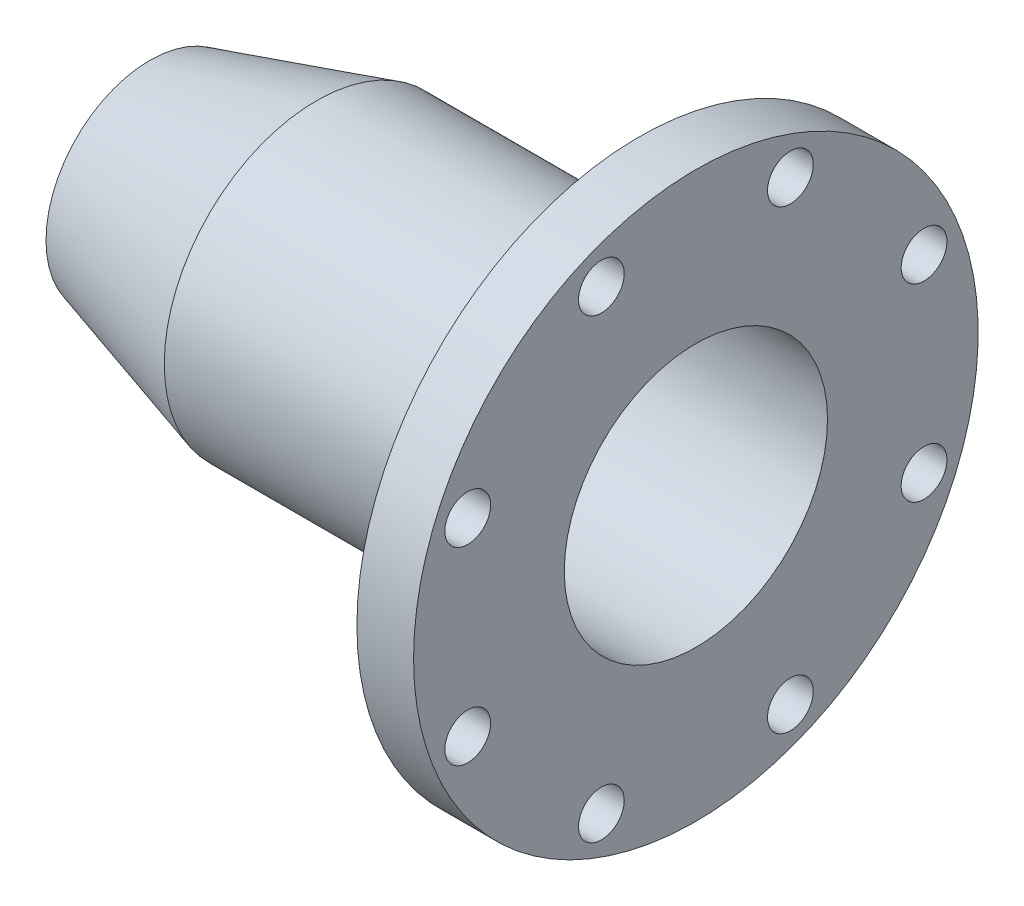
SolidWorks part; units mm, degrees
ref_plane "Front Plane" through (0, 0, 0) normal (0, 0, 1) x (1, 0, 0)
ref_plane "Top Plane" through (0, 0, 0) normal (0, 1, 0) x (1, 0, 0)
ref_plane "Right Plane" through (0, 0, 0) normal (1, 0, 0) x (0, 0, -1)
sketch "Sketch1" plane through (0, 0, 0) normal (0, 0, 1) x (1, 0, 0)
  line L0 (0, 0) -> (541.4119, 0) construction
  line L1 (266.7, 64.295) -> (266.7, 137.92)
  line L2 (266.7, 137.92) -> (239.01, 137.92)
  line L3 (239.01, 137.92) -> (239.01, 74.295)
  line L4 (239.01, 74.295) -> (81.28, 74.295)
  line L5 (239.01, 64.295) -> (82.6963, 64.295)
  line L6 (239.01, 64.295) -> (266.7, 64.295)
  line L7 (81.28, 74.295) -> (0, 50.8)
  line L8 (82.6963, 64.295) -> (0, 40.3906)
  line L9 (0, 50.8) -> (0, 40.3906)
  dimension "D2" = 27.69
  dimension "D3" = 74.295
  dimension "D4" = 185.42
  dimension "D5" = 266.7
  dimension "D6" = 10
  dimension "D1" = 50.8
  dimension "D7" = 10
revolve "Revolve1" add sketch "Sketch1" angle 360 about L0
sketch "Sketch3" plane through (266.7, 0, 0) normal (1, 0, 0) x (0, 0, -1)
  line L0 (0, 0) -> (0, 120.65) construction
  line L1 (0, 0) -> (-46.1708, 111.4661) construction
  circle A0 centre (0, 0) radius 120.65 construction
  dimension "D1" = 241.3
  dimension "D2" = 22.5
hole_wizard "1/16 (0.88) Diameter Hole1" positions "3DSketch2" profile "Sketch7" hole size "1/16" standard "ANSI Inch" end condition through all
sketch3d "3DSketch2"
  point P0 (266.7, 111.4661, 46.1708)
sketch "Sketch7" plane through (266.7, 111.4661, 46.1708) normal (0, 1, 0) x (0, 0, -1)
  line L0 (0, 0) -> (0, 266.7)
  line L1 (0, 266.7) -> (11.176, 266.7)
  line L2 (11.176, 266.7) -> (11.176, 0)
  line L5 (11.176, 0) -> (0, 0)
  line L11 (0, -6.35) -> (0, 107.95) construction
  dimension "Thru Hole Dia." = 22.352
  dimension "Thru Hole Depth" = 266.7
pattern_circular "CirPattern1" count 8 every 45 about axis through (0, 0, 0) along (-1, 0, 0) of "1/16 (0.88) Diameter Hole1"
equation "\"Wall Thickness\"= 10"
equation "\"D6@Sketch1\"=\"Wall Thickness\""
equation "\"Nozzle diameter\"= 4 * 25.4"
equation "\"D1@Sketch1\"=\"Nozzle diameter\"/2"
equation "\"D7@Sketch1\"=\"Wall Thickness\""
